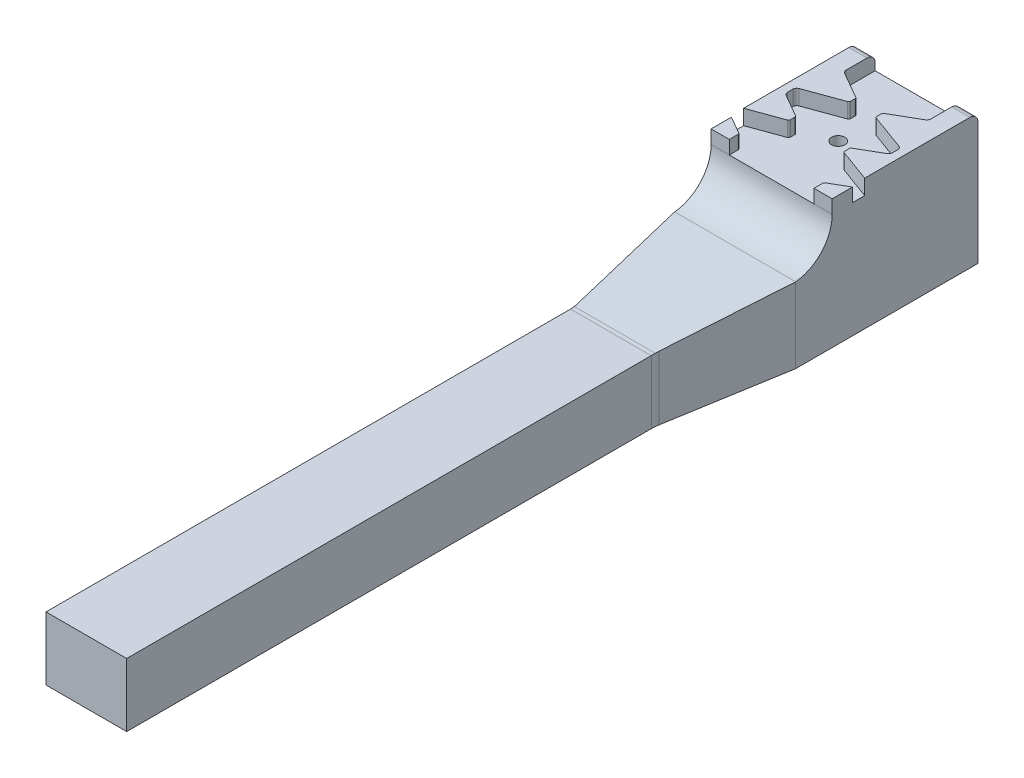
SolidWorks part; units mm, degrees
material "AISI Type A2 Tool Steel"
ref_plane "Front Plane" through (0, 0, 0) normal (0, 0, 1) x (1, 0, 0)
ref_plane "Top Plane" through (0, 0, 0) normal (0, 1, 0) x (1, 0, 0)
ref_plane "Right Plane" through (0, 0, 0) normal (1, 0, 0) x (0, 0, -1)
sketch "Sketch1" plane through (0, 0, 0) normal (1, 0, 0) x (0, 0, -1)
  line L1 (0, 0) -> (202, 0)
  line L2 (0, 0) -> (0, 15.7)
  line L3 (0, 15.7) -> (130, 15.7)
  line L4 (160.817, 18.6469) -> (130.967, 15.7469)
  line L6 (202, 28.6) -> (169.85, 28.6)
  line L12 (202, 0) -> (202, 28.6)
  arc A0 (130, 15.7) -> (130.967, 15.7469) centre (130, 25.7) ccw
  arc A1 (160.817, 18.6469) -> (169.85, 28.6) centre (159.85, 28.6) ccw
  dimension "D1" = 20
  dimension "D5" = 130
  dimension "D6" = 10
  dimension "D2" = 12.9
  dimension "D3" = 15.7
  dimension "D4" = 32.15
  dimension "D7" = 169.85
extrude "Boss-Extrude1" add sketch "Sketch1" along normal blind 15
sketch "Sketch2" plane through (0, 28.6, 0) normal (0, 1, 0) x (1, 0, 0)
  line L0 (15, 160.817) -> (15, 0)
  line L1 (15, 0) -> (10, 0)
  line L2 (15, 0) -> (0, 0) construction
  line L3 (10, 0) -> (10, 130.967)
  line L5 (0, 130) -> (0, 0) construction
  line L6 (15, 130.967) -> (0, 130.967) construction
  line L7 (15, 160.817) -> (10, 130.967)
  dimension "D1" = 10
extrude "Cut-Extrude1" cut sketch "Sketch2" against normal through all
mirror "Mirror1" about plane through (0, 25.7, -130) normal (1, 0, 0) of bodies 102 103
fillet "Congé2" radius 10 2 edges at (-10, 7.8734, -130.967) (10, 7.8734, -130.967)
sketch "Sketch3" plane through (0, 28.6, 0) normal (0, 1, 0) x (1, 0, 0)
  line L0 (-10, 169.85) -> (-10, 172)
  line L1 (15, 169.85) -> (-15, 169.85) construction
  line L2 (-10, 172) -> (-15, 174.8868)
  line L3 (-15, 174.8868) -> (-15, 177.3868) construction
  line L5 (-15, 177.3868) -> (-6.5, 180.4805)
  line L6 (-6.5, 180.4805) -> (-6.5, 182.4805)
  line L7 (-6.5, 182.4805) -> (-12.5, 185.9446)
  line L8 (-12.5, 185.9446) -> (-12.5, 188.4446)
  line L9 (-12.5, 188.4446) -> (-3, 191.9023)
  line L10 (-3, 191.9023) -> (-3, 193.9023)
  line L11 (-3, 193.9023) -> (-10, 197.9438)
  line L12 (-10, 197.9438) -> (-10, 202)
  line L13 (15, 202) -> (-15, 202) construction
  line L14 (-10, 202) -> (-15, 202)
  line L16 (-15, 169.85) -> (-10, 169.85)
  line L17 (0, 169.85) -> (0, 202) construction
  line L18 (-15, 169.85) -> (-15, 174.8868)
  line L19 (-15, 177.3868) -> (-15, 202)
  line L20 (-15, 202) -> (-15, 169.85) construction
  dimension "D1" = 10
  dimension "D2" = 110
  dimension "D3" = 120
  dimension "D4" = 4.0562
  dimension "D5" = 15
  dimension "D6" = 2.5
  dimension "D7" = 6.5
  dimension "D8" = 120
  dimension "D9" = 2
  dimension "D10" = 2.5
  dimension "D11" = 12.5
  dimension "D12" = 3
  dimension "D13" = 2
  dimension "D14" = 10
extrude "Boss-Extrude2" add sketch "Sketch3" along normal blind 3.75
sketch "Sketch4" plane through (0, 32.35, 0) normal (0, 1, 0) x (1, 0, 0)
  line L0 (-10, 172) -> (-15, 174.8868) construction
  line L1 (-10, 169.85) -> (-10.5, 169.85)
  line L2 (-10, 169.85) -> (-10, 172.2887)
  line L3 (-10, 172.2887) -> (-10.5, 172.2887)
  line L4 (-10.5, 169.85) -> (-10.5, 172.2887)
  line L7 (-15, 177.9188) -> (-6.75, 180.9216)
  line L8 (-6.75, 180.9216) -> (-6.75, 182.6248)
  line L9 (-6.5, 182.4805) -> (-12.5, 185.9446) construction
  line L10 (-6.75, 182.6248) -> (-6.5, 182.4805)
  line L11 (-6.5, 182.4805) -> (-6.5, 180.4805)
  line L12 (-6.5, 180.4805) -> (-15, 177.3868)
  line L14 (-12.5, 185.9446) -> (-13, 186.2333)
  line L15 (-13, 186.2333) -> (-13, 188.7947)
  line L16 (-13, 188.7947) -> (-3.25, 192.3434)
  line L17 (-3.25, 192.3434) -> (-3.25, 194.0467)
  line L18 (-3, 193.9023) -> (-10, 197.9438) construction
  line L19 (-3.25, 194.0467) -> (-3, 193.9023)
  line L20 (-3, 193.9023) -> (-3, 191.9023)
  line L21 (-3, 191.9023) -> (-12.5, 188.4446)
  line L22 (-12.5, 188.4446) -> (-12.5, 185.9446)
  line L23 (-6.5, 182.4805) -> (-12.5, 185.9446) construction
  line L24 (-10, 197.9438) -> (-10.5, 198.2324)
  line L25 (-10.5, 198.2324) -> (-10.5, 202)
  line L26 (-10, 202) -> (-15, 202) construction
  line L27 (-10.5, 202) -> (-10, 202)
  line L28 (-10, 202) -> (-10, 197.9438)
  line L29 (-15, 202) -> (-15, 177.3868) construction
  line L30 (-15, 177.9188) -> (-15, 177.3868)
  dimension "D1" = 0.5
  dimension "D3" = 0.5
  dimension "D4" = 0.25
  dimension "D5" = 0.25
  dimension "D6" = 0.5
  dimension "D7" = 0.5
  dimension "D8" = 0.5
extrude "Cut-Extrude2" cut sketch "Sketch4" against normal up to surface (3.75 mm away) up to face at (-6, 28.6, -184.9337)
fillet "Fillet1" radius 0.5 5 edges at (-3.25, 30.475, -194.0467) (-3.25, 30.475, -192.3434) (-6.75, 30.475, -182.6248) (-6.75, 30.475, -180.9216) (-10.5, 30.475, -172.2887)
fillet "Fillet2" radius 1 3 edges at (-10.5, 30.475, -198.2324) (-13, 30.475, -188.7947) (-13, 30.475, -186.2333)
mirror "Mirror2" about plane through (0, 0, 0) normal (1, 0, 0) of "Fillet2", "Fillet1", "Cut-Extrude2", "Boss-Extrude2"
hole_wizard "M4 Tapped Hole1" positions "Sketch6" profile "Sketch7" tap size "M4" standard "ISO"
sketch "Sketch6" plane through (0, 28.6, 0) normal (0, 1, 0) x (1, 0, 0)
  line L0 (10.5, 169.85) -> (-10.5, 169.85) construction
  line L1 (0, 186.35) -> (0, 202)
  line L2 (10.5, 202) -> (-10.5, 202) construction
  point P0 (0, 186.35)
  dimension "D1" = 16.5
sketch "Sketch7" plane through (0, 28.6, -186.35) normal (1, 0, 0) x (0, 0, 1)
  line L0 (0, 0) -> (0, 12.4914)
  line L1 (0, 12.4914) -> (1.65, 11.5)
  line L2 (1.65, 11.5) -> (1.65, 0)
  line L5 (1.65, 0) -> (0, 0)
  line L10 (0, 12.4914) -> (-1.65, 11.5) construction
  line L11 (0, -6.35) -> (0, 107.95) construction
  dimension "Tap Drill Dia." = 3.3
  dimension "Tap Drill Depth" = 11.5
  dimension "Drill Angle" = 118
cosmetic thread "Hole Thread1" parameters "D1"=8, "D2"=4
sketch "Sketch8" plane through (0, 0, -202) normal (0, 0, -1) x (-1, 0, 0)
  line L0 (-10.5, 32.35) -> (-15, 32.35)
  line L1 (-15, 32.35) -> (-15, 0)
  line L2 (-15, 0) -> (15, 0)
  line L3 (15, 0) -> (15, 32.35)
  line L4 (15, 32.35) -> (10.5, 32.35)
  line L5 (10.5, 32.35) -> (10.5, 28.6)
  line L6 (10.5, 28.6) -> (-10.5, 28.6)
  line L7 (-10.5, 28.6) -> (-10.5, 32.35)
extrude "Boss-Extrude3" add sketch "Sketch8" along normal blind 4
sketch "Sketch9" plane through (0, 32.35, 0) normal (0, 1, 0) x (1, 0, 0)
  line L1 (15, 169.85) -> (-15, 169.85)
  line L2 (15, 169.85) -> (15, 174.8868)
  line L3 (15, 174.8868) -> (-15, 174.8868)
  line L4 (-15, 169.85) -> (-15, 174.8868)
extrude "Cut-Extrude3" cut sketch "Sketch9" against normal blind 0.4
fillet "Fillet3" radius 2 2 edges at (-12.75, 32.35, -206) (12.75, 32.35, -206)
